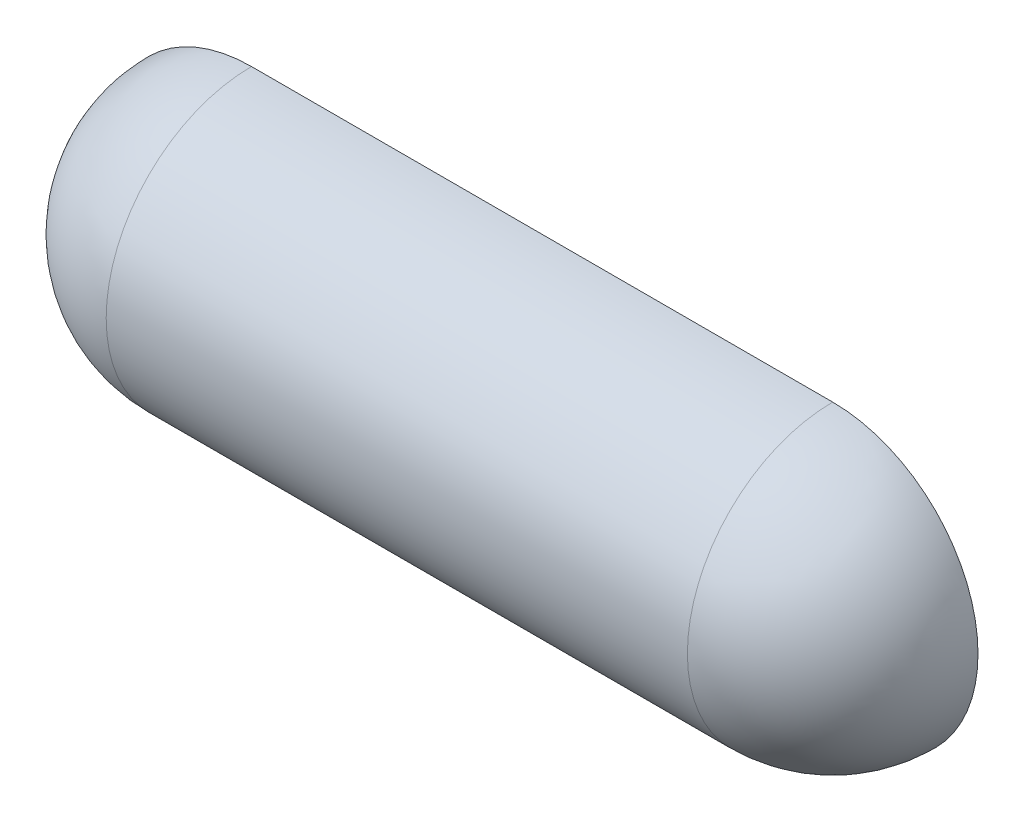
SolidWorks part; units mm, degrees
ref_plane "Front Plane" through (0, 0, 0) normal (0, 0, 1) x (1, 0, 0)
ref_plane "Top Plane" through (0, 0, 0) normal (0, 1, 0) x (1, 0, 0)
ref_plane "Right Plane" through (0, 0, 0) normal (1, 0, 0) x (0, 0, -1)
sketch "Sketch1" plane through (0, 0, 0) normal (0, 0, 1) x (1, 0, 0)
  line L0 (0, -652.3429) -> (0, 1677.7917) construction
  line L5 (-75, 0) -> (375, 0)
  line L6 (0, 75) -> (300, 75)
  line L7 (-75, -11.1998) -> (-75, 194.1976) construction
  line L8 (375, -55.0873) -> (375, 140.9739) construction
  arc A4 (0, 75) -> (-75, 0) centre (0, 0) ccw
  arc A5 (300, 75) -> (375, 0) centre (300, 0) cw
  point P13 (0, 0)
  dimension "D1" = 75
  dimension "D2" = 300
revolve "Revolve1" add sketch "Sketch1" angle 180 about L5
ref_axis "Axis1" through (0, 0, -3.75) along (0, 0, 1)
ref_plane "Plane1" through (300, 0, 0) normal (1, 0, 0) x (0, 0, -1)
ref_axis "Axis2" through (300, 0, 17.5) along (0, 0, -1)
equation "\"link2_diameter\"=150"
equation "\"link2_length\"=300"
equation "\"link3_diameter\"=150"
equation "\"link3_length\"=150"
equation "\"link4_diameter\"=150"
equation "\"link4_length\"=150"
equation "\"link5_diameter\"=150"
equation "\"link5_length\"=200"
equation "\"end_effector_diameter\"=150"
equation "\"end_effector_length\"=150"
equation "\"base_link_diameterA\"=200"
equation "\"base_link_diameterB\"=150"
equation "\"base_link_length\"=150"
equation "\"base_link_lengthA\"=50"
equation "\"link1_diameter\"=150"
equation "\"link1_length\"=150"
equation "\"D1@Sketch1\"=\"link2_diameter\"/2"
equation "\"D2@Sketch1\"=\"link2_length\""
